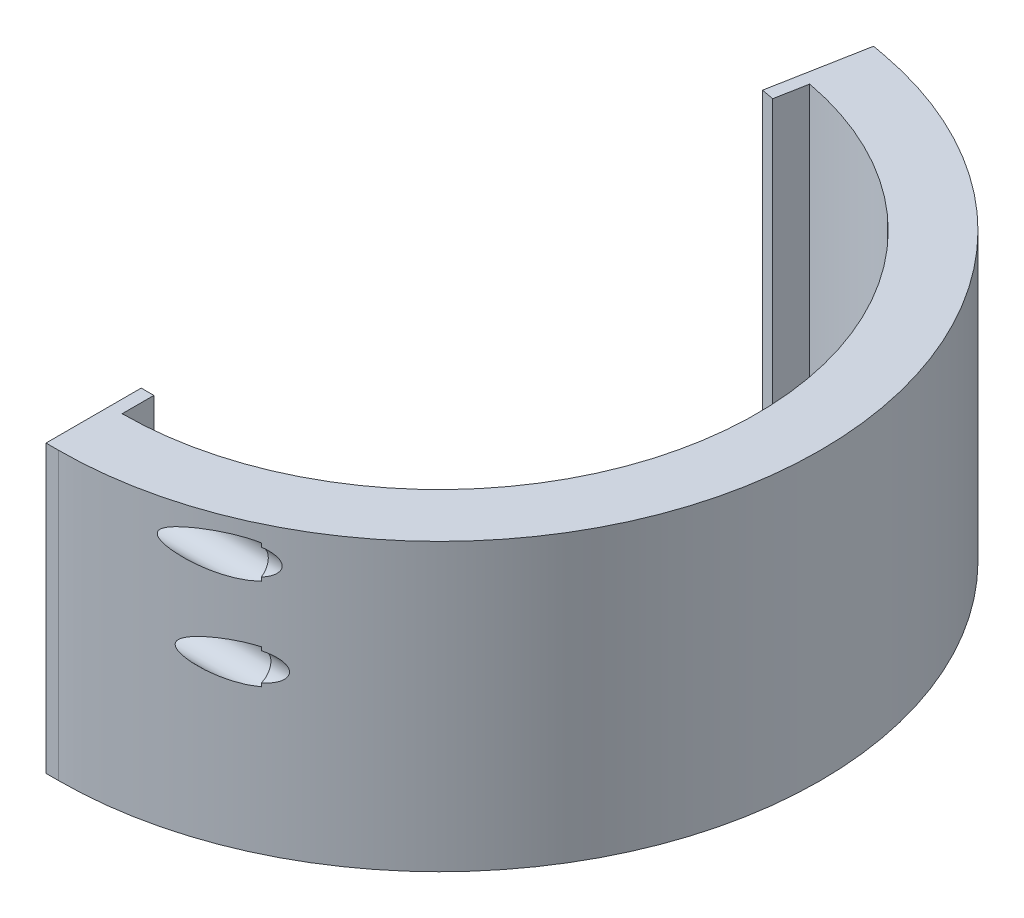
SolidWorks part; units mm, degrees
ref_plane "Front Plane" through (0, 0, 0) normal (0, 0, 1) x (1, 0, 0)
ref_plane "Top Plane" through (0, 0, 0) normal (0, 1, 0) x (1, 0, 0)
ref_plane "Right Plane" through (0, 0, 0) normal (1, 0, 0) x (0, 0, -1)
sketch "Sketch1" plane through (0, 0, 0) normal (0, 1, 0) x (1, 0, 0)
  line L0 (70.209, 37.4518) -> (69.0426, 31.2098)
  line L1 (63.2107, -31.75) -> (63.2107, -38.1)
  line L2 (69.0426, 31.2098) -> (70.209, 37.4518)
  line L3 (69.0426, 31.2098) -> (70.209, 37.4518)
  line L4 (69.0426, 31.2098) -> (67.7942, 31.4431)
  line L5 (70.209, 37.4518) -> (68.9606, 37.685)
  line L6 (67.7942, 31.4431) -> (68.9606, 37.685)
  line L7 (67.7942, 31.4431) -> (69.0426, 31.2098)
  line L8 (67.7942, 31.4431) -> (67.211, 28.3221)
  line L9 (69.0426, 31.2098) -> (68.4594, 28.0888)
  line L10 (67.211, 28.3221) -> (68.4594, 28.0888)
  line L13 (63.2107, -38.1) -> (63.2107, -31.75)
  line L14 (63.2107, -38.1) -> (61.9407, -38.1)
  line L15 (63.2107, -31.75) -> (61.9407, -31.75)
  line L16 (61.9407, -38.1) -> (61.9407, -31.75)
  line L17 (61.9407, -31.75) -> (63.2107, -31.75)
  line L18 (61.9407, -31.75) -> (61.9407, -28.575)
  line L19 (63.2107, -31.75) -> (63.2107, -28.575)
  line L20 (61.9407, -28.575) -> (63.2107, -28.575)
  arc A0 (63.2107, -38.1) -> (70.209, 37.4518) centre (63.2107, 0) ccw
  arc A1 (69.5289, -31.115) -> (75.1366, 29.4251) centre (63.2107, 0) ccw
  arc A2 (69.0426, 31.2098) -> (75.1366, 29.4251) centre (63.2107, 0) cw
  arc A3 (69.5289, -31.115) -> (63.2107, -31.75) centre (63.2107, 0) cw
  point P8 (69.0426, 0)
  point P18 (69.0426, 0)
  dimension "D1" = 38.1
  dimension "D3" = 31.75
  dimension "D2" = 1.27
  dimension "D4" = 6.35
  dimension "D5" = 6.242
  dimension "D6" = 3.175
  dimension "D7" = 3.175
  dimension "D8" = 1.27
extrude "Boss-Extrude1" add sketch "Sketch1" along normal blind 27.94 contours A1 A3 L1 A0 L0 A2 | L8 L10 L9 L4 | L6 L4 L0 L5 | L16 L14 L1 L15 | L20 L18 L15 L19 region at (100.3058, 0, 3.4361) region at (69.0016, 0, -34.4474) region at (68.1268, 0, -29.766) region at (62.5757, 0, 34.925) region at (62.5757, 0, 30.1625)
sketch "Sketch2" plane through (61.9407, 0, 0) normal (-1, 0, 0) x (0, 0, 1)
  circle A0 centre (34.8775, 15.559) radius 1.5
  circle A1 centre (35.1915, 24.6339) radius 1.5549
  circle A2 centre (-35.1708, 24.6339) radius 1.5192
  circle A3 centre (-35.1708, 15.364) radius 1.5
  circle A4 centre (34.8775, 15.559) radius 1.8175
  circle A5 centre (35.1915, 24.6339) radius 1.8724
  circle A6 centre (-35.1708, 24.6339) radius 1.8367
  circle A7 centre (-35.1708, 15.364) radius 1.8175
extrude "Cut-Extrude1" cut sketch "Sketch2" against normal through all and the other way through all contours A0 | A1 | A2 | A3 region at (61.9407, 15.559, 34.8775) region at (61.9407, 24.6339, 35.1915) region at (61.9407, 24.6339, -35.1708) region at (61.9407, 15.364, -35.1708)
extrude "Cut-Extrude2" cut sketch "Sketch2<3>" against normal blind 17.78 contours A4 A0 | A5 A1 | A6 A2 | A7 A3 region at (61.9407, 15.559, 33.1114) region at (61.9407, 24.6339, 33.3721) region at (61.9407, 24.6339, -36.9556) region at (61.9407, 15.364, -36.9369)
sketch "Sketch2<3>" plane through (61.9407, 0, 0) normal (-1, 0, 0) x (0, 0, 1) same geometry as "Sketch2"
extrude "Boss-Extrude2" add sketch "Sketch1<2>" against normal blind 0.6858 contours A1 A3 L1 A0 L0 A2 | L6 L4 L0 L5 | L8 L10 L9 L4 | L16 L14 L1 L15 | L20 L18 L15 L19 region at (100.3058, 0, 3.4361) region at (69.0016, 0, -34.4474) region at (68.1268, 0, -29.766) region at (62.5757, 0, 34.925) region at (62.5757, 0, 30.1625)
sketch "Sketch1<2>" plane through (0, 0, 0) normal (0, 1, 0) x (1, 0, 0) same geometry as "Sketch1"
